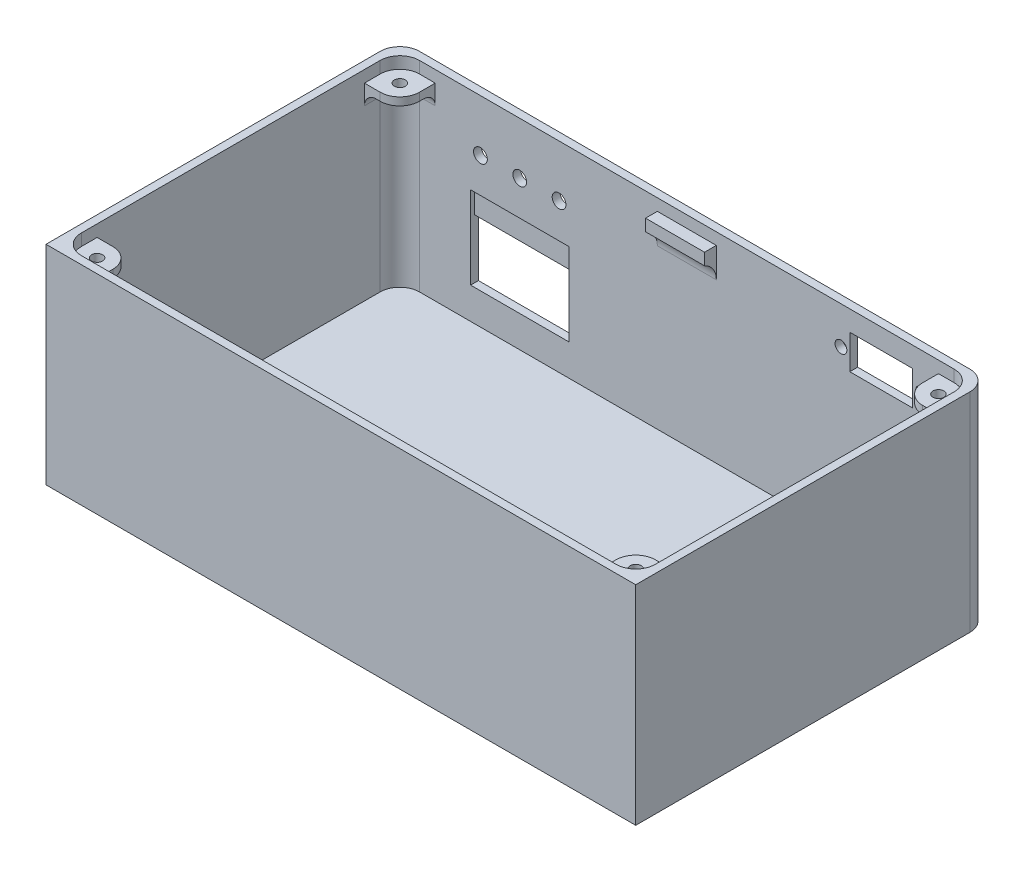
SolidWorks part; units mm, degrees
ref_plane "Front Plane" through (0, 0, 0) normal (0, 0, 1) x (1, 0, 0)
ref_plane "Top Plane" through (0, 0, 0) normal (0, 1, 0) x (1, 0, 0)
ref_plane "Right Plane" through (0, 0, 0) normal (1, 0, 0) x (0, 0, -1)
sketch "Sketch1" plane through (0, 0, 0) normal (0, 1, 0) x (1, 0, 0)
  line L1 (-75.1327, 42.0133) -> (74.8673, 42.0133)
  line L2 (-75.1327, 42.0133) -> (-75.1327, -47.9867)
  line L3 (-75.1327, -47.9867) -> (74.8673, -47.9867)
  line L4 (74.8673, 42.0133) -> (74.8673, -47.9867)
  dimension "D1" = 90
  dimension "D2" = 150
extrude "Boss-Extrude1" add sketch "Sketch1" along normal blind 50
shell "Shell1" thickness 2
sketch "Sketch2" plane through (0, 50, 0) normal (0, 1, 0) x (1, 0, 0)
  line L0 (-73.1327, -36.9867) -> (-73.1327, -45.9867)
  line L1 (-73.1327, 40.0133) -> (-64.1327, 40.0133)
  line L2 (-73.1327, 40.0133) -> (-73.1327, 31.0133)
  line L3 (-73.1327, 31.0133) -> (-64.1327, 31.0133)
  line L4 (-64.1327, 40.0133) -> (-64.1327, 31.0133)
  line L5 (-64.1327, -36.9867) -> (-64.1327, -45.9867)
  line L6 (-73.1327, -36.9867) -> (-64.1327, -36.9867)
  line L7 (-73.1327, -45.9867) -> (-64.1327, -45.9867)
  line L8 (63.8673, -36.9867) -> (63.8673, -45.9867)
  line L9 (63.8673, -36.9867) -> (72.8673, -36.9867)
  line L10 (63.8673, -45.9867) -> (72.8673, -45.9867)
  line L11 (72.8673, -36.9867) -> (72.8673, -45.9867)
  line L12 (63.8673, 40.0133) -> (72.8673, 40.0133)
  line L13 (63.8673, 31.0133) -> (72.8673, 31.0133)
  line L14 (72.8673, 40.0133) -> (72.8673, 31.0133)
  line L15 (63.8673, 40.0133) -> (63.8673, 31.0133)
  line L16 (72.8673, -45.9867) -> (72.8673, 40.0133) construction
  line L17 (72.8673, -45.9867) -> (72.8673, 40.0133) construction
extrude "Boss-Extrude2" add sketch "Sketch2" against normal blind 2
sketch "Sketch5" plane through (74.8673, 0, 0) normal (1, 0, 0) x (0, 0, -1)
  line L1 (-47.9867, 0) -> (42.0133, -51.9615)
ref_plane "Plane1" through (0, -20.7789, 11.9967) normal (0, 0.866, -0.5) x (0, -0.5, -0.866)
sketch "Sketch10" plane through (0, 50, 0) normal (0, 1, 0) x (1, 0, 0)
  line L1 (-68.6327, 35.5133) -> (-64.1327, 35.5133) construction
  line L2 (-64.1327, 31.0133) -> (-64.1327, 40.0133) construction
  line L3 (-64.1327, 35.5133) -> (-68.6327, 35.5133) construction
  line L4 (-68.6327, 35.5133) -> (-68.6327, 31.0133) construction
  line L5 (-73.1327, 31.0133) -> (-64.1327, 31.0133) construction
  line L6 (-68.6327, 35.5133) -> (-68.6327, 40.0133) construction
  line L7 (-64.1327, 40.0133) -> (-68.6327, 40.0133) construction
  line L8 (63.8673, 40.0133) -> (72.8673, 31.0133) construction
  line L9 (72.8673, -45.9867) -> (72.8673, 40.0133) construction
  line L10 (72.8673, -36.9867) -> (72.8673, 31.0133) construction
  line L11 (63.8673, -45.9867) -> (72.8673, -36.9867) construction
  line L12 (-64.1327, -45.9867) -> (-73.1327, -36.9867) construction
  circle A0 centre (-68.6327, 35.5133) radius 1.4
  circle A1 centre (-68.6327, -41.4867) radius 1.4
  circle A2 centre (68.3673, -41.4867) radius 1.4
  circle A3 centre (68.3673, 35.5133) radius 1.4
extrude "Cut-Extrude5" cut sketch "Sketch10" against normal blind 14
sketch "Sketch13" plane through (-75.1327, 0, 0) normal (-1, 0, 0) x (0, 0, 1)
  line L0 (47.9867, 0) -> (45.9867, -5)
  line L1 (47.9867, 0) -> (35.9867, 0)
  line L5 (35.9867, -5) -> (35.9867, 0)
  circle A2 centre (40.9867, -5) radius 1.9
  arc A3 (35.9867, -5) -> (45.9867, -5) centre (40.9867, -5) ccw
  dimension "D1" = 12
  dimension "D2" = 5
  dimension "D3" = 5
extrude "Boss-Extrude4" add sketch "Sketch13" against normal up to surface (150 mm away) up to face at (74.8673, 25, 2.9867)
sketch "Sketch14" plane through (0, 0, 0) normal (0, -1, 0) x (1, 0, 0)
  line L5 (-76.2024, 47.9867) -> (75.9171, 47.9867)
  line L6 (-76.2024, 47.9867) -> (-76.2024, 33.9867)
  line L7 (-76.2024, 33.9867) -> (75.9171, 33.9867)
  line L8 (75.9171, 47.9867) -> (75.9171, 33.9867)
extrude "Cut-Extrude7" cut sketch "Sketch14" along normal blind 176
sketch "Sketch15" plane through (0, 50, 0) normal (0, 1, 0) x (1, 0, 0)
  line L0 (72.8673, 40.0133) -> (-73.1327, 40.0133) construction
  line L1 (-75.1327, 42.0133) -> (74.8673, 42.0133)
  line L2 (-75.1327, 42.0133) -> (-75.1327, -47.9867)
  line L3 (-75.1327, -47.9867) -> (74.8673, -47.9867)
  line L4 (74.8673, 42.0133) -> (74.8673, -47.9867)
  line L5 (-73.1327, 40.0133) -> (72.0442, 40.0133)
  line L6 (-73.1327, 40.0133) -> (-73.1327, -45.9867)
  line L7 (-73.1327, -45.9867) -> (72.0442, -45.9867)
  line L9 (-73.1327, 40.0133) -> (-73.1327, -45.9867) construction
  line L10 (-73.1327, -45.9867) -> (72.8673, -45.9867) construction
  line L11 (72.8673, -36.9867) -> (72.8673, 31.0133) construction
  line L12 (72.8673, -36.9867) -> (72.8673, 31.0133)
  line L13 (72.8673, 31.0133) -> (72.8673, 40.0133)
  line L14 (72.8673, 40.0133) -> (72.0442, 40.0133)
  line L15 (72.0442, -45.9867) -> (72.8673, -45.9867)
  line L16 (72.8673, -45.9867) -> (72.8673, -36.9867)
extrude "Boss-Extrude5" add sketch "Sketch15" along normal blind 3
sketch "Sketch16" plane through (0, 0, -40.0133) normal (0, 0, 1) x (1, 0, 0)
  line L0 (-7.6327, 50) -> (7.3673, 50)
  line L2 (7.3673, 47) -> (-7.6327, 47)
  line L3 (-7.6327, 47) -> (-7.6327, 50)
  line L4 (7.3673, 47) -> (7.3673, 50)
  point P9 (-0.1327, 47)
extrude "Boss-Extrude6" add sketch "Sketch16" along normal blind 3
ref_plane "Plane2" through (0, 0, 2.9867) normal (0, 0, 1) x (1, 0, 0)
mirror "Mirror1" about plane through (0, 0, 2.9867) normal (0, 0, 1) of "Boss-Extrude6"
fillet "Fillet1" radius 5 4 edges at (63.8673, 49, -31.0133) (63.8673, 49, 36.9867) (-64.1327, 49, 36.9867) (-64.1327, 49, -31.0133)
sketch "Sketch17" plane through (0, 2, 0) normal (0, 1, 0) x (1, 0, 0)
  circle A2 centre (-25.1327, -2.9867) radius 7
  circle A3 centre (24.8673, -2.9867) radius 7
  point P0 (-0.1327, -2.9867)
  point P9 (-0.1327, -2.9867)
extrude "Cut-Extrude8" cut sketch "Sketch17" against normal blind 10
sketch "Sketch19" plane through (0, 0, -42.0133) normal (0, 0, -1) x (-1, 0, 0)
  line L0 (75.1327, 53) -> (75.1327, 0) construction
  line L1 (55.1327, 25) -> (30.1327, 25)
  line L2 (55.1327, 25) -> (55.1327, 10)
  line L3 (55.1327, 10) -> (30.1327, 10)
  line L4 (30.1327, 25) -> (30.1327, 10)
  line L5 (-74.8673, 0) -> (75.1327, 0) construction
  line L6 (-49.3173, 39.15) -> (-49.3173, 47.85) construction
  line L7 (-35.7673, 37.5) -> (-62.8673, 37.5) construction
  line L8 (-35.7673, 37.5) -> (-35.7673, 49.5) construction
  line L9 (-35.7673, 49.5) -> (-62.8673, 49.5) construction
  line L10 (-62.8673, 37.5) -> (-62.8673, 49.5) construction
  line L11 (-59.5673, 43.5) -> (-39.0673, 43.5) construction
  line L12 (-41.3173, 39.15) -> (-57.3173, 39.15)
  line L13 (-41.3173, 39.15) -> (-41.3173, 47.85)
  line L14 (-41.3173, 47.85) -> (-57.3173, 47.85)
  line L15 (-57.3173, 47.85) -> (-57.3173, 39.15)
  line L16 (52.6327, 39.8103) -> (42.6327, 39.8103) construction
  line L17 (-74.8673, 53) -> (75.1327, 53) construction
  line L18 (-74.8673, 53) -> (-74.8673, 0) construction
  line L19 (42.6327, 25) -> (42.6327, 35) construction
  line L20 (42.6327, 39.8103) -> (32.6327, 39.8103) construction
  line L21 (-38.2828, 37.5) -> (-57.3173, 47.85) construction
  circle A0 centre (-39.0673, 43.5) radius 1.5
  circle A1 centre (-59.5673, 43.5) radius 1.5
  circle A2 centre (52.6327, 39.8103) radius 1.75
  circle A3 centre (42.6327, 39.8103) radius 1.75
  circle A4 centre (32.6327, 39.8103) radius 1.75
  circle A6 centre (22.6327, 39.8103) radius 1.75 [skipped]
  point P17 (-49.3173, 43.5)
  point P20 (-49.3173, 43.5)
  point P23 (-49.3173, 39.15)
  dimension "D3" = 3.3
  dimension "D13" = 4
  dimension "D1" = 20
  dimension "D2" = 10
  dimension "D5" = 16
  dimension "D6" = 8.7
  dimension "D7" = 27.1
  dimension "D8" = 12
  dimension "D9" = 6
  dimension "D10" = 20.5
  dimension "D11" = 3.5
  dimension "D12" = 12
  dimension "D14" = 10
  dimension "D15" = 10
extrude "Cut-Extrude9" cut sketch "Sketch19" against normal blind 10
sketch "Sketch21" plane through (0, 0, -42.0133) normal (0, 0, -1) x (-1, 0, 0)
  line L0 (54.2479, 46.4566) -> (23.942, 46.4566) construction
  text T0 "+      -     M\r\n"
extrude "Cut-Extrude10" cut sketch "Sketch21" against normal blind 0.5
sketch "Sketch23" plane through (0, 0, -40.0133) normal (0, 0, 1) x (1, 0, 0)
  line L5 (-30.1327, 10) -> (-55.1327, 10)
  line L6 (-30.1327, 10) -> (-30.1327, 31)
  line L7 (-30.1327, 31) -> (-55.1327, 31)
  line L8 (-55.1327, 10) -> (-55.1327, 31)
extrude "Cut-Extrude12" cut sketch "Sketch23" against normal blind 1
fillet "Fillet2" radius 5 16 edges at (-73.1327, 51.5, 45.9867) (72.8673, 51.5, 45.9867) (72.8673, 51.5, -40.0133) (-73.1327, 51.5, -40.0133) (-0.1327, 47, -40.0133) (-7.6327, 47, -38.5133) (7.3673, 47, -38.5133) (-7.6327, 47, 44.4867) (7.3673, 47, 44.4867) (-0.1327, 47, 45.9867) (72.8673, 25, -40.0133) (-73.1327, 25, -40.0133) (72.8673, 25, 45.9867) (-73.1327, 25, 45.9867) (-75.1327, 26.5, -42.0133) (74.8673, 26.5, -42.0133)
fillet "Fillet3" radius 3 12 edges at (72.8673, 48, 38.9867) (65.8673, 48, 45.9867) (65.8673, 48, -40.0133) (72.8673, 48, -33.0133) (-73.1327, 48, -33.0133) (-66.1327, 48, -40.0133) (-66.1327, 48, 45.9867) (-73.1327, 48, 38.9867) (71.4028, 48, 44.5223) (71.4028, 48, -38.5488) (-71.6683, 48, -38.5488) (-71.6683, 48, 44.5223)
sketch "Sketch24" plane through (0, 0, 0) normal (0, -1, 0) x (1, 0, 0)
  point P0 (-25.1327, 2.9867)
  point P1 (24.8673, 2.9867)
